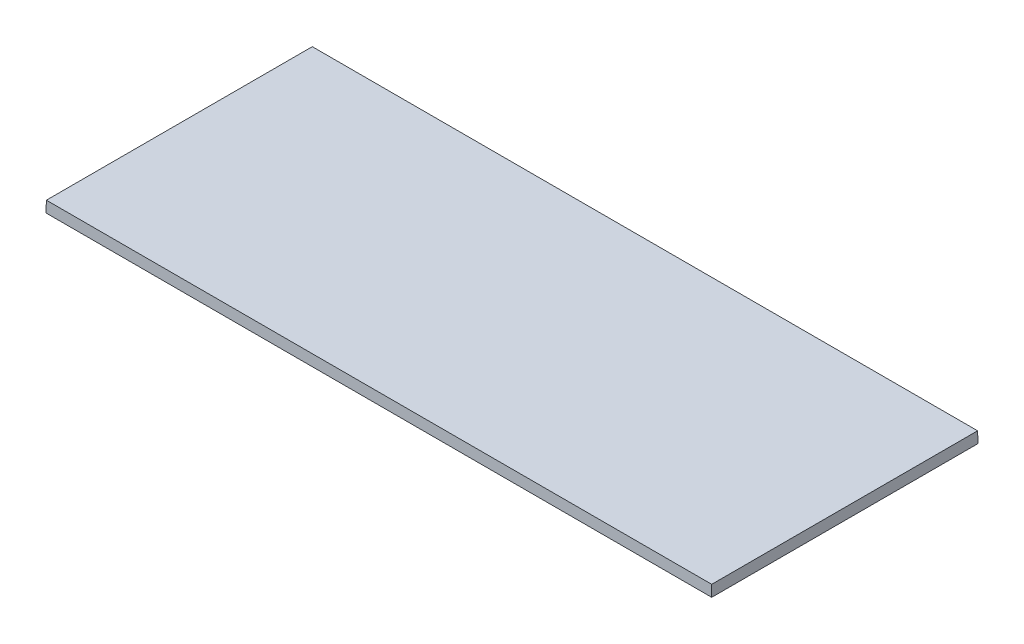
SolidWorks part; units mm, degrees
ref_plane "Front Plane" through (0, 0, 0) normal (0, 0, 1) x (1, 0, 0)
ref_plane "Top Plane" through (0, 0, 0) normal (0, 1, 0) x (1, 0, 0)
ref_plane "Right Plane" through (0, 0, 0) normal (1, 0, 0) x (0, 0, -1)
sketch "Sketch1" plane through (0, 0, 0) normal (0, 1, 0) x (1, 0, 0)
  line L1 (-150, -60) -> (150, -60)
  line L2 (-150, -60) -> (-150, 60)
  line L3 (-150, 60) -> (150, 60)
  line L4 (150, -60) -> (150, 60)
  line L5 (-150, -60) -> (150, 60) construction
  line L6 (-150, 60) -> (150, -60) construction
  point P0 (0, 0)
extrude "Boss-Extrude1" add sketch "Sketch1" along normal blind 5 draft 1
shell "Shell1" thickness 1 removed face at (0, 0, 0)
ref_plane "Plane1" through (0, 0, 0) normal (0, -1, 0) x (-1, 0, 0)
